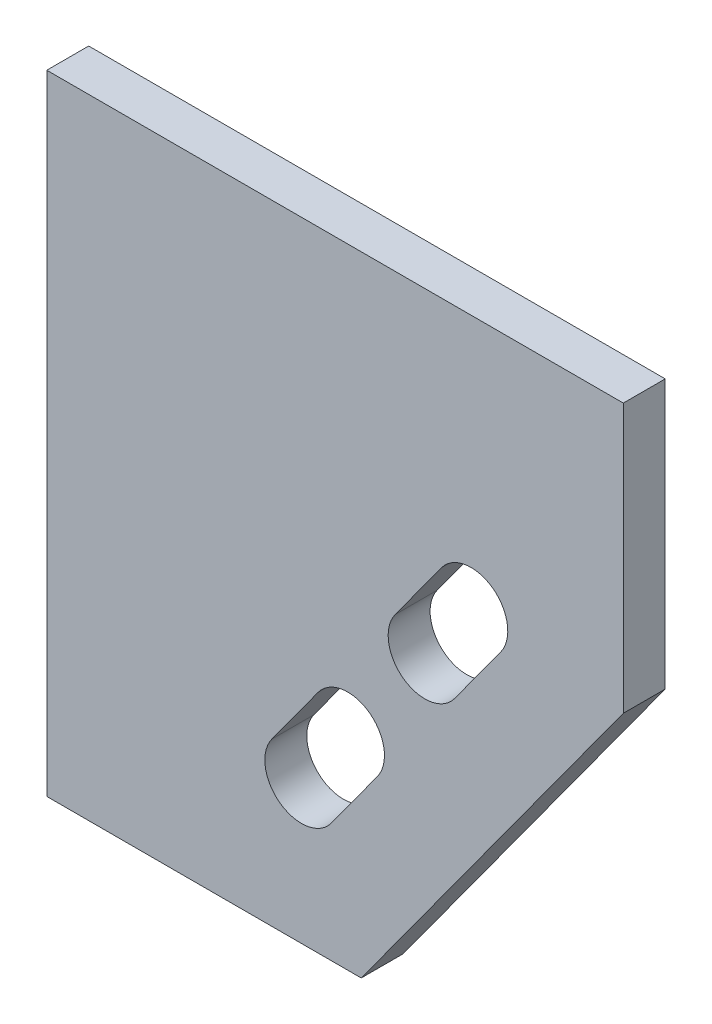
SolidWorks part; units mm, degrees
material "Простая углеродистая сталь"
ref_plane "Спереди" through (0, 0, 0) normal (0, 0, 1) x (1, 0, 0)
ref_plane "Сверху" through (0, 0, 0) normal (0, 1, 0) x (1, 0, 0)
ref_plane "Справа" through (0, 0, 0) normal (1, 0, 0) x (0, 0, -1)
sketch "Эскиз1" plane through (0, 0, 0) normal (0, 0, 1) x (1, 0, 0)
  line L0 (0, 0) -> (0, 120)
  line L1 (0, 120) -> (110, 120)
  line L2 (110, 120) -> (110, 68.7386)
  line L3 (110, 68.7386) -> (60, 0)
  line L4 (60, 0) -> (0, 0)
  dimension "D1" = 85
  dimension "D2" = 120
  dimension "D3" = 60
  dimension "D4" = 110
base flange "Базовая кромка1" sketch "Эскиз1" thickness 8 reverse thickness direction no parameters "D1"=1
sketch "Эскиз6" plane through (0, 0, 0) normal (0, 0, 1) x (1, 0, 0)
  line L0 (85, 34.3693) -> (67.991, 46.7415) construction
  line L1 (60, 0) -> (110, 68.7386) construction
  line L2 (72.1357, 59.1838) -> (80.9592, 71.3142) construction
  line L3 (66.4749, 63.3015) -> (75.2984, 75.4318)
  line L4 (77.7965, 55.0662) -> (86.6201, 67.1965)
  line L5 (57.4298, 38.9666) -> (48.6063, 26.8362) construction
  line L6 (51.769, 43.0842) -> (42.9455, 30.9539)
  line L7 (63.0906, 34.8489) -> (54.2671, 22.7186)
  arc A0 (66.4749, 63.3015) -> (77.7965, 55.0662) centre (72.1357, 59.1838) ccw
  arc A1 (86.6201, 67.1965) -> (75.2984, 75.4318) centre (80.9592, 71.3142) ccw
  arc A2 (51.769, 43.0842) -> (63.0906, 34.8489) centre (57.4298, 38.9666) cw
  arc A3 (54.2671, 22.7186) -> (42.9455, 30.9539) centre (48.6063, 26.8362) cw
  point P6 (76.5475, 65.249)
  point P13 (53.018, 32.9014)
  dimension "D4" = 15
  dimension "D1" = 14
  dimension "D2" = 25
  dimension "D3" = 40
extrude "Вырез-Вытянуть1" cut sketch "Эскиз6" against normal blind 10 normal cut yes
sketch "Сгиб-Линии1" [suppressed] plane through (0, 0, 0) normal (0, 1, 0) x (1, 0, 0)
sketch "Граничная рамка1" [suppressed] plane through (0, 0, 0) normal (0, 1, 0) x (1, 0, 0)
sheet metal parameters "Листовой металл1" thickness 8 parameters "D1"=1
flat pattern "Развертка1" [suppressed]
sketch "Сгиб-Линии2" plane through (0, 0, 0) normal (0, 1, 0) x (1, 0, 0)
sketch "Граничная рамка2" [suppressed] plane through (0, 0, 0) normal (0, 1, 0) x (1, 0, 0)
sheet metal parameters "Листовой металл2" thickness 8 parameters "D1"=1
flat pattern "Развертка1"
sketch "Сгиб-Линии2" plane through (0, 0, 0) normal (0, 1, 0) x (1, 0, 0)
sketch3d "Граничная рамка2" [suppressed]
  line L0 (110, 120, 0) -> (110, 0, 0) construction
  line L1 (0, 120, 0) -> (0, 0, 0) construction
  line L2 (110, 120, 0) -> (0, 120, 0) construction
  line L3 (110, 0, 0) -> (0, 0, 0) construction
